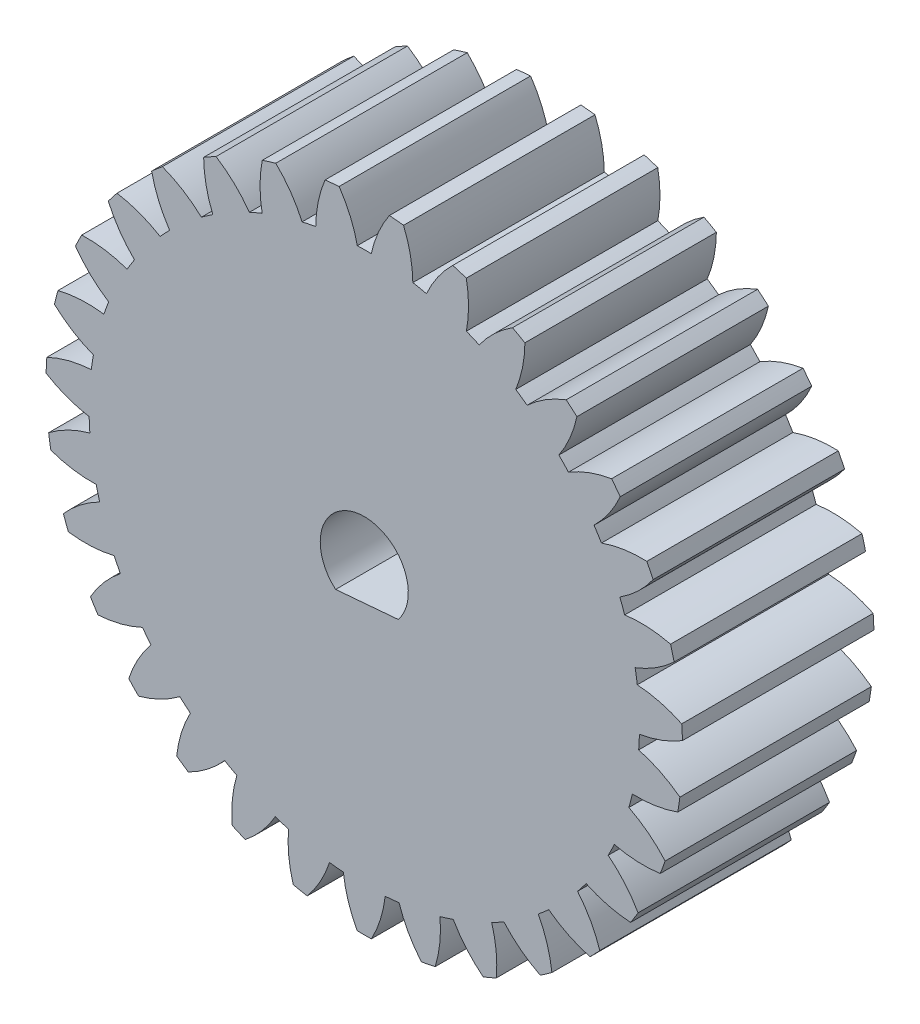
SolidWorks part; units mm, degrees
ref_plane "Front Plane" through (0, 0, 0) normal (0, 0, 1) x (1, 0, 0)
ref_plane "Top Plane" through (0, 0, 0) normal (0, 1, 0) x (1, 0, 0)
ref_plane "Right Plane" through (0, 0, 0) normal (1, 0, 0) x (0, 0, -1)
sketch "Model" plane through (0, 0, 0) normal (0, 0, 1) x (1, 0, 0)
  line L2 (-1.4964, -1.7466) -> (1.7687, -1.4702)
  arc A1 (1.7687, -1.4702) -> (-1.4964, -1.7466) centre (0, 0) ccw
  arc A124 (14.3694, -0.3649) -> (16.6183, 0.4718) centre (13.3283, 5.8738) ccw
  arc A126 (16.6183, 0.4718) -> (16.5808, 1.2118) centre (0, 0) ccw
  arc A127 (16.5808, 1.2118) -> (14.2587, 1.8167) centre (13.8542, -4.4953) ccw
  arc A128 (14.2587, 1.8167) -> (14.1487, 2.5351) centre (0, 0) ccw
  arc A129 (14.1487, 2.5351) -> (16.1831, 3.8074) centre (11.8731, 8.4366) ccw
  arc A130 (16.1831, 3.8074) -> (15.9974, 4.5247) centre (0, 0) ccw
  arc A131 (15.9974, 4.5247) -> (13.6011, 4.6498) centre (14.4755, -1.6145) ccw
  arc A132 (13.6011, 4.6498) -> (13.3487, 5.3313) centre (0, 0) ccw
  arc A133 (13.3487, 5.3313) -> (15.0854, 6.9871) centre (9.9318, 10.6539) ccw
  arc A134 (15.0854, 6.9871) -> (14.7591, 7.6523) centre (0, 0) ccw
  arc A135 (14.7591, 7.6523) -> (12.3867, 7.2925) centre (14.5042, 1.3325) ccw
  arc A136 (12.3867, 7.2925) -> (12.0023, 7.9093) centre (0, 0) ccw
  arc A137 (12.0023, 7.9093) -> (13.3701, 9.8808) centre (7.5838, 12.4351) ccw
  arc A138 (13.3701, 9.8808) -> (12.9166, 10.4667) centre (0, 0) ccw
  arc A139 (12.9166, 10.4667) -> (10.6652, 9.6367) centre (13.939, 4.2249) ccw
  arc A140 (10.6652, 9.6367) -> (10.1645, 10.1634) centre (0, 0) ccw
  arc A141 (10.1645, 10.1634) -> (11.1075, 12.3699) centre (4.9254, 13.7072) ccw
  arc A142 (11.1075, 12.3699) -> (10.5453, 12.8525) centre (0, 0) ccw
  arc A143 (10.5453, 12.8525) -> (8.507, 11.5863) centre (12.8032, 6.9443) ccw
  arc A144 (8.507, 11.5863) -> (7.9105, 12.0015) centre (0, 0) ccw
  arc A145 (7.9105, 12.0015) -> (8.3901, 14.3526) centre (2.0654, 14.4181) ccw
  arc A146 (8.3901, 14.3526) -> (7.7422, 14.7122) centre (0, 0) ccw
  arc A147 (7.7422, 14.7122) -> (6.0006, 13.0616) centre (11.1433, 9.3794) ccw
  arc A148 (6.0006, 13.0616) -> (5.3327, 13.3482) centre (0, 0) ccw
  arc A149 (5.3327, 13.3482) -> (5.3291, 15.7477) centre (-0.8792, 14.5387) ccw
  arc A150 (5.3291, 15.7477) -> (4.6222, 15.9695) centre (0, 0) ccw
  arc A151 (4.6222, 15.9695) -> (3.2485, 14.0021) centre (9.0271, 11.4305) ccw
  arc A152 (3.2485, 14.0021) -> (2.5366, 14.1484) centre (0, 0) ccw
  arc A153 (2.5366, 14.1484) -> (2.0501, 16.4981) centre (-3.7878, 14.0641) ccw
  arc A154 (2.0501, 16.4981) -> (1.3129, 16.5731) centre (0, 0) ccw
  arc A155 (1.3129, 16.5731) -> (0.3634, 14.3694) centre (6.5414, 13.0137) ccw
  arc A156 (0.3634, 14.3694) -> (-0.3634, 14.3694) centre (0, 0) ccw
  arc A157 (-0.3634, 14.3694) -> (-1.3129, 16.5731) centre (-6.5414, 13.0137) ccw
  arc A158 (-1.3129, 16.5731) -> (-2.0501, 16.4981) centre (0, 0) ccw
  arc A159 (-2.0501, 16.4981) -> (-2.5366, 14.1484) centre (3.7878, 14.0641) ccw
  arc A160 (-2.5366, 14.1484) -> (-3.2485, 14.0021) centre (0, 0) ccw
  arc A161 (-3.2485, 14.0021) -> (-4.6222, 15.9695) centre (-9.0271, 11.4305) ccw
  arc A162 (-4.6222, 15.9695) -> (-5.3291, 15.7477) centre (0, 0) ccw
  arc A163 (-5.3291, 15.7477) -> (-5.3327, 13.3482) centre (0.8792, 14.5387) ccw
  arc A164 (-5.3327, 13.3482) -> (-6.0006, 13.0616) centre (0, 0) ccw
  arc A165 (-6.0006, 13.0616) -> (-7.7422, 14.7122) centre (-11.1433, 9.3794) ccw
  arc A166 (-7.7422, 14.7122) -> (-8.3901, 14.3526) centre (0, 0) ccw
  arc A167 (-8.3901, 14.3526) -> (-7.9105, 12.0015) centre (-2.0654, 14.4181) ccw
  arc A168 (-7.9105, 12.0015) -> (-8.507, 11.5863) centre (0, 0) ccw
  arc A169 (-8.507, 11.5863) -> (-10.5453, 12.8525) centre (-12.8032, 6.9443) ccw
  arc A170 (-10.5453, 12.8525) -> (-11.1075, 12.3699) centre (0, 0) ccw
  arc A171 (-11.1075, 12.3699) -> (-10.1645, 10.1634) centre (-4.9254, 13.7072) ccw
  arc A172 (-10.1645, 10.1634) -> (-10.6652, 9.6367) centre (0, 0) ccw
  arc A173 (-10.6652, 9.6367) -> (-12.9166, 10.4667) centre (-13.939, 4.2249) ccw
  arc A174 (-12.9166, 10.4667) -> (-13.3701, 9.8808) centre (0, 0) ccw
  arc A175 (-13.3701, 9.8808) -> (-12.0023, 7.9093) centre (-7.5838, 12.4351) ccw
  arc A176 (-12.0023, 7.9093) -> (-12.3867, 7.2925) centre (0, 0) ccw
  arc A177 (-12.3867, 7.2925) -> (-14.7591, 7.6523) centre (-14.5042, 1.3325) ccw
  arc A178 (-14.7591, 7.6523) -> (-15.0854, 6.9871) centre (0, 0) ccw
  arc A179 (-15.0854, 6.9871) -> (-13.3487, 5.3313) centre (-9.9318, 10.6539) ccw
  arc A180 (-13.3487, 5.3313) -> (-13.6011, 4.6498) centre (0, 0) ccw
  arc A181 (-13.6011, 4.6498) -> (-15.9974, 4.5247) centre (-14.4755, -1.6145) ccw
  arc A182 (-15.9974, 4.5247) -> (-16.1831, 3.8074) centre (0, 0) ccw
  arc A183 (-16.1831, 3.8074) -> (-14.1487, 2.5351) centre (-11.8731, 8.4366) ccw
  arc A184 (-14.1487, 2.5351) -> (-14.2587, 1.8167) centre (0, 0) ccw
  arc A185 (-14.2587, 1.8167) -> (-16.5808, 1.2118) centre (-13.8542, -4.4953) ccw
  arc A186 (-16.5808, 1.2118) -> (-16.6183, 0.4718) centre (0, 0) ccw
  arc A187 (-16.6183, 0.4718) -> (-14.3694, -0.3649) centre (-13.3283, 5.8738) ccw
  arc A188 (-14.3694, -0.3649) -> (-14.3326, -1.0907) centre (0, 0) ccw
  arc A189 (-14.3326, -1.0907) -> (-16.4853, -2.1507) centre (-12.6657, -7.1921) ccw
  arc A190 (-16.4853, -2.1507) -> (-16.3731, -2.883) centre (0, 0) ccw
  arc A191 (-16.3731, -2.883) -> (-14.0018, -3.2499) centre (-14.2379, 3.0706) ccw
  arc A192 (-14.0018, -3.2499) -> (-13.8196, -3.9535) centre (0, 0) ccw
  arc A193 (-13.8196, -3.9535) -> (-15.7149, -5.4251) centre (-10.9587, -9.5945) ccw
  arc A194 (-15.7149, -5.4251) -> (-15.4576, -6.1199) centre (0, 0) ccw
  arc A195 (-15.4576, -6.1199) -> (-13.0609, -6.002) centre (-14.5645, 0.1417) ccw
  arc A196 (-13.0609, -6.002) -> (-12.7409, -6.6544) centre (0, 0) ccw
  arc A197 (-12.7409, -6.6544) -> (-14.3012, -8.4775) centre (-8.803, -11.604) ccw
  arc A198 (-14.3012, -8.4775) -> (-13.9092, -9.1062) centre (0, 0) ccw
  arc A199 (-13.9092, -9.1062) -> (-11.5854, -8.5082) centre (-14.2949, -2.793) ccw
  arc A200 (-11.5854, -8.5082) -> (-11.1406, -9.083) centre (0, 0) ccw
  arc A201 (-11.1406, -9.083) -> (-12.3019, -11.1827) centre (-6.2869, -13.1385) ccw
  arc A202 (-12.3019, -11.1827) -> (-11.7915, -11.7197) centre (0, 0) ccw
  arc A203 (-11.7915, -11.7197) -> (-9.6356, -10.6662) centre (-13.4401, -5.6134) ccw
  arc A204 (-9.6356, -10.6662) -> (-9.0841, -11.1396) centre (0, 0) ccw
  arc A205 (-9.0841, -11.1396) -> (-9.799, -13.4302) centre (-3.5134, -14.1351) ccw
  arc A206 (-9.799, -13.4302) -> (-9.1909, -13.8534) centre (0, 0) ccw
  arc A207 (-9.1909, -13.8534) -> (-7.2912, -12.3875) centre (-12.035, -8.2039) ccw
  arc A208 (-7.2912, -12.3875) -> (-6.6558, -12.7402) centre (0, 0) ccw
  arc A209 (-6.6558, -12.7402) -> (-6.895, -15.1278) centre (-0.5961, -14.553) ccw
  arc A210 (-6.895, -15.1278) -> (-6.2141, -15.42) centre (0, 0) ccw
  arc A211 (-6.2141, -15.42) -> (-4.6484, -13.6016) centre (-10.1372, -10.4586) ccw
  arc A212 (-4.6484, -13.6016) -> (-3.955, -13.8192) centre (0, 0) ccw
  arc A213 (-3.955, -13.8192) -> (-3.7086, -16.2061) centre (2.3456, -14.3751) ccw
  arc A214 (-3.7086, -16.2061) -> (-2.9829, -16.3552) centre (0, 0) ccw
  arc A215 (-2.9829, -16.3552) -> (-1.8152, -14.2589) centre (-7.8244, -12.2852) ccw
  arc A216 (-1.8152, -14.2589) -> (-1.0922, -14.3324) centre (0, 0) ccw
  arc A217 (-1.0922, -14.3324) -> (-0.3705, -16.6209) centre (5.1912, -13.6087) ccw
  arc A218 (-0.3705, -16.6209) -> (0.3705, -16.6209) centre (0, 0) ccw
  arc A219 (0.3705, -16.6209) -> (1.0922, -14.3324) centre (-5.1912, -13.6087) ccw
  arc A220 (1.0922, -14.3324) -> (1.8152, -14.2589) centre (0, 0) ccw
  arc A221 (1.8152, -14.2589) -> (2.9829, -16.3552) centre (7.8244, -12.2852) ccw
  arc A222 (2.9829, -16.3552) -> (3.7086, -16.2061) centre (0, 0) ccw
  arc A223 (3.7086, -16.2061) -> (3.955, -13.8192) centre (-2.3456, -14.3751) ccw
  arc A224 (3.955, -13.8192) -> (4.6484, -13.6016) centre (0, 0) ccw
  arc A225 (4.6484, -13.6016) -> (6.2141, -15.42) centre (10.1372, -10.4586) ccw
  arc A226 (6.2141, -15.42) -> (6.895, -15.1278) centre (0, 0) ccw
  arc A227 (6.895, -15.1278) -> (6.6558, -12.7402) centre (0.5961, -14.553) ccw
  arc A228 (6.6558, -12.7402) -> (7.2912, -12.3875) centre (0, 0) ccw
  arc A229 (7.2912, -12.3875) -> (9.1909, -13.8534) centre (12.035, -8.2039) ccw
  arc A230 (9.1909, -13.8534) -> (9.799, -13.4302) centre (0, 0) ccw
  arc A231 (9.799, -13.4302) -> (9.0841, -11.1396) centre (3.5134, -14.1351) ccw
  arc A232 (9.0841, -11.1396) -> (9.6356, -10.6662) centre (0, 0) ccw
  arc A233 (9.6356, -10.6662) -> (11.7915, -11.7197) centre (13.4401, -5.6134) ccw
  arc A234 (11.7915, -11.7197) -> (12.3019, -11.1827) centre (0, 0) ccw
  arc A235 (12.3019, -11.1827) -> (11.1406, -9.083) centre (6.2869, -13.1385) ccw
  arc A236 (11.1406, -9.083) -> (11.5854, -8.5082) centre (0, 0) ccw
  arc A237 (11.5854, -8.5082) -> (13.9092, -9.1062) centre (14.2949, -2.793) ccw
  arc A238 (13.9092, -9.1062) -> (14.3012, -8.4775) centre (0, 0) ccw
  arc A239 (14.3012, -8.4775) -> (12.7409, -6.6544) centre (8.803, -11.604) ccw
  arc A240 (12.7409, -6.6544) -> (13.0609, -6.002) centre (0, 0) ccw
  arc A241 (13.0609, -6.002) -> (15.4576, -6.1199) centre (14.5645, 0.1417) ccw
  arc A242 (15.4576, -6.1199) -> (15.7149, -5.4251) centre (0, 0) ccw
  arc A243 (15.7149, -5.4251) -> (13.8196, -3.9535) centre (10.9587, -9.5945) ccw
  arc A244 (13.8196, -3.9535) -> (14.0018, -3.2499) centre (0, 0) ccw
  arc A245 (14.0018, -3.2499) -> (16.3731, -2.883) centre (14.2379, 3.0706) ccw
  arc A246 (16.3731, -2.883) -> (16.4853, -2.1507) centre (0, 0) ccw
  arc A247 (16.4853, -2.1507) -> (14.3326, -1.0907) centre (12.6657, -7.1921) ccw
  arc A248 (14.3326, -1.0907) -> (14.3694, -0.3649) centre (0, 0) ccw
extrude "Boss-Extrude1" add sketch "Model" along normal blind 10
